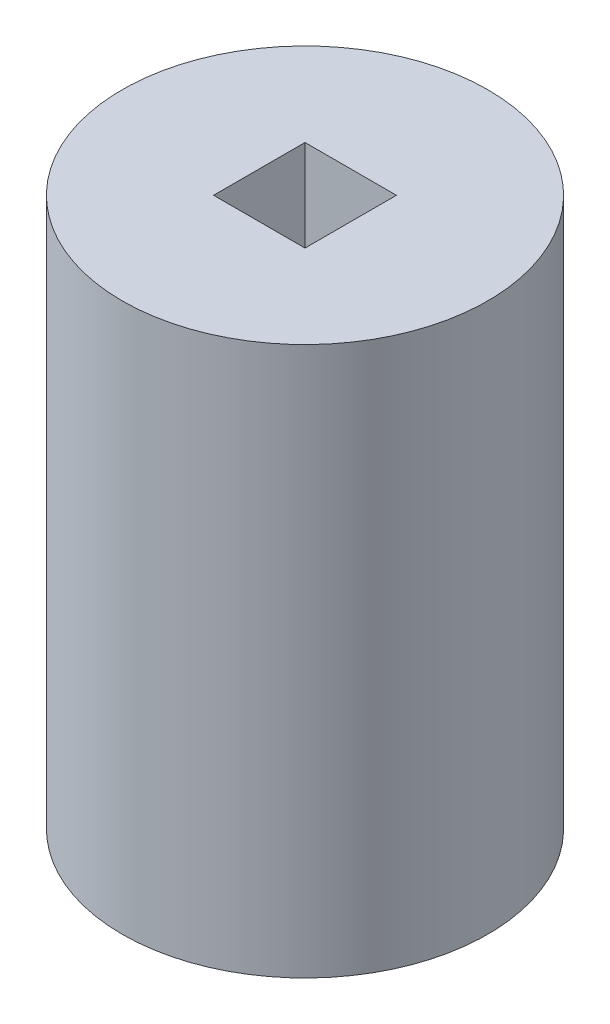
SolidWorks part; units mm, degrees
ref_plane "Front Plane" through (0, 0, 0) normal (0, 0, 1) x (1, 0, 0)
ref_plane "Top Plane" through (0, 0, 0) normal (0, 1, 0) x (1, 0, 0)
ref_plane "Right Plane" through (0, 0, 0) normal (1, 0, 0) x (0, 0, -1)
sketch "Sketch1" plane through (0, 0, 0) normal (0, 1, 0) x (1, 0, 0)
  circle A0 centre (0, 0) radius 5
  dimension "D1" = 10
extrude "Boss-Extrude1" add sketch "Sketch1" along normal blind 15
sketch "Sketch2" plane through (0, 0, 0) normal (0, -1, 0) x (1, 0, 0)
  circle A0 centre (0, 0) radius 2.5
  dimension "D1" = 5
extrude "Cut-Extrude1" cut sketch "Sketch2" against normal blind 5
sketch "Sketch3" plane through (0, 15, 0) normal (0, 1, 0) x (1, 0, 0)
  line L1 (-1.25, -1.25) -> (1.25, -1.25)
  line L2 (-1.25, -1.25) -> (-1.25, 1.25)
  line L3 (-1.25, 1.25) -> (1.25, 1.25)
  line L4 (1.25, -1.25) -> (1.25, 1.25)
  line L5 (-1.25, -1.25) -> (1.25, 1.25) construction
  line L6 (-1.25, 1.25) -> (1.25, -1.25) construction
  point P0 (0, 0)
  dimension "D1" = 2.5
extrude "Cut-Extrude2" cut sketch "Sketch3" against normal blind 5
